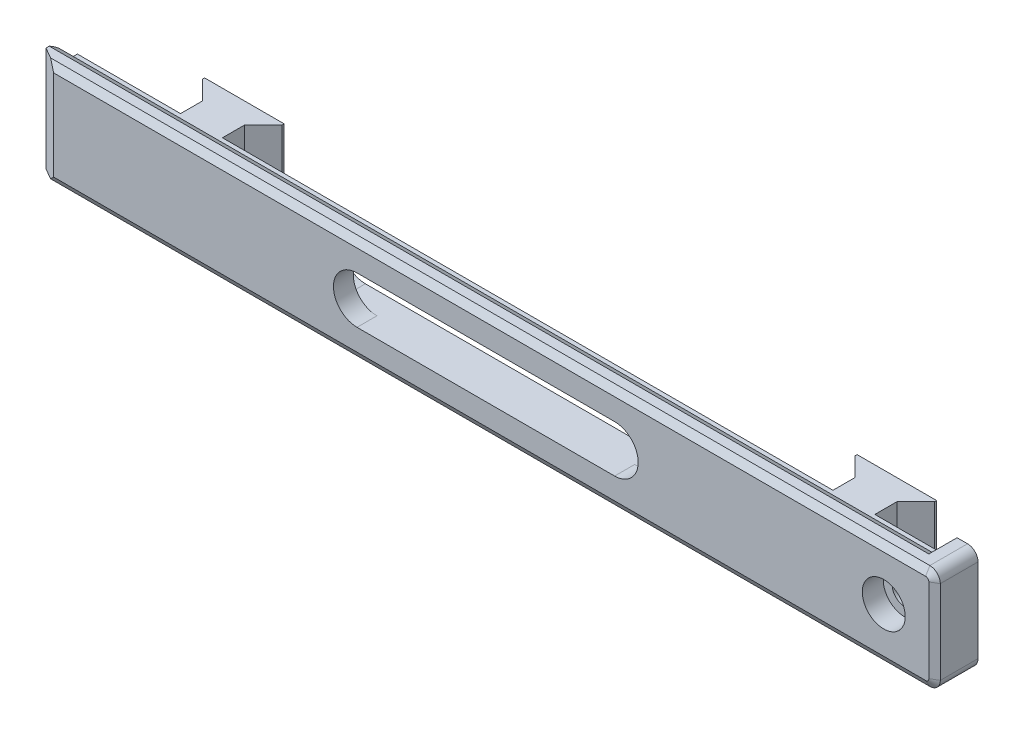
SolidWorks part; units mm, degrees
note: The reader was unsure of these and kept them because the rebuilt part matched: shared geometry of "草图2<3>", "草图5<3>".
ref_plane "前视基准面" through (0, 0, 0) normal (0, 0, 1) x (1, 0, 0)
ref_plane "上视基准面" through (0, 0, 0) normal (0, 1, 0) x (1, 0, 0)
ref_plane "右视基准面" through (0, 0, 0) normal (1, 0, 0) x (0, 0, -1)
sketch "草图1" plane through (0, 0, 0) normal (0, 1, 0) x (1, 0, 0)
  line L0 (-46.8887, 0) -> (50.4859, 0) construction
  line L1 (-43, 2) -> (-33.15, 2)
  line L2 (-43, 2) -> (-43, -2)
  line L3 (-43, -2) -> (43, -2)
  line L4 (43, 2) -> (43, -2)
  line L5 (-43, 2) -> (43, -2) construction
  line L6 (-43, -2) -> (43, 2) construction
  line L7 (-31.15, 5.5725) -> (-31.15, -8.0763) construction
  line L8 (0, -7.558) -> (0, 8.5096) construction
  line L9 (31.15, 4.9966) -> (31.15, -6.291) construction
  line L10 (-33.15, 4.1) -> (-33.15, 2)
  line L14 (-29.15, 4.1) -> (-29.15, 2)
  line L15 (-29.15, 4.1) -> (-27.35, 5.9)
  line L17 (-34.95, 6.1) -> (-27.35, 6.1)
  line L18 (-34.95, 6.1) -> (-34.95, 5.9)
  line L20 (-27.35, 6.1) -> (-27.35, 5.9)
  line L21 (29.15, 4.1) -> (29.15, 2)
  line L22 (33.15, 4.1) -> (33.15, 2)
  line L23 (-29.15, 2) -> (29.15, 2)
  line L24 (-33.15, 4.1) -> (-34.95, 5.9)
  line L25 (33.15, 4.1) -> (34.95, 5.9)
  line L26 (27.35, 6.1) -> (34.95, 6.1)
  line L27 (27.35, 6.1) -> (27.35, 5.9)
  line L28 (34.95, 6.1) -> (34.95, 5.9)
  line L29 (29.15, 4.1) -> (27.35, 5.9)
  line L30 (33.15, 2) -> (43, 2)
  point P0 (0, 0)
  dimension "D1" = 86
  dimension "D2" = 4
  dimension "D3" = 62.3
  dimension "D4" = 31.15
  dimension "D5" = 4
  dimension "D6" = 7.6
  dimension "D7" = 135
  dimension "D8" = 2
  dimension "D9" = 135
  dimension "D10" = 2.1
  dimension "D11" = 4
  dimension "D12" = 135
  dimension "D13" = 135
  dimension "D14" = 2.1
  dimension "D15" = 2
  dimension "D16" = 7.6
extrude "凸台-拉伸1" add sketch "草图1" along normal blind 6
sketch "草图2" plane through (0, 0, -2) normal (0, 0, -1) x (-1, 0, 0)
  line L0 (-12.3, 3) -> (12.3, 3) construction
  line L1 (-12.3, 5.25) -> (12.3, 5.25)
  line L2 (-12.3, 0.75) -> (12.3, 0.75)
  line L3 (-29.15, 6) -> (29.15, 6) construction
  line L4 (-29.15, 0) -> (29.15, 0) construction
  line L5 (0, 0) -> (0, 5.646) construction
  line L6 (-15.5, 3) -> (15.5, 3) construction
  line L7 (-15.5, 5.25) -> (15.5, 5.25)
  line L8 (-15.5, 0.75) -> (15.5, 0.75)
  arc A0 (-12.3, 5.25) -> (-12.3, 0.75) centre (-12.3, 3) ccw
  arc A1 (12.3, 0.75) -> (12.3, 5.25) centre (12.3, 3) ccw
  arc A2 (-15.5, 5.25) -> (-15.5, 0.75) centre (-15.5, 3) ccw
  arc A3 (15.5, 0.75) -> (15.5, 5.25) centre (15.5, 3) ccw
  point P2 (0, 3)
  point P15 (0, 3)
  dimension "D1" = 24.6
  dimension "D2" = 4.5
  dimension "D3" = 31
extrude "切除-拉伸1" cut sketch "草图2" against normal blind 2.1 contours A2 L8 A3 L7
extrude "切除-拉伸2" cut sketch "草图2<3>" against normal blind 4 contours A0 L2 A1 L1
sketch "草图2<3>" plane through (0, 0, -2) normal (0, 0, -1) x (-1, 0, 0) same geometry as "草图2"
sketch "草图3" plane through (0, 0, 2) normal (0, 0, 1) x (1, 0, 0)
  line L0 (43, 6) -> (43, 0) construction
  line L1 (-43, 8) -> (43, 8)
  line L2 (-43, 8) -> (-43, 6)
  line L3 (-43, -2) -> (43, -2)
  line L4 (43, 8) -> (43, 6)
  line L5 (-43, 6) -> (-43, 0) construction
  line L6 (-43, 6) -> (43, 6) construction
  line L7 (-43, 0) -> (43, 0) construction
  line L10 (-43, 0) -> (43, 0)
  line L11 (-43, 6) -> (43, 6)
  line L12 (-43, 0) -> (-43, -2)
  line L13 (43, 0) -> (43, -2)
  dimension "D2" = 2
  dimension "D3" = 2
extrude "凸台-拉伸2" add sketch "草图3" against normal blind 2
sketch "草图4" plane through (0, 0, 2) normal (0, 0, 1) x (1, 0, 0)
  line L0 (43, 8) -> (-43, 8) construction
  line L1 (43, -2) -> (41, -2)
  line L2 (43, -2) -> (43, 8)
  line L3 (43, 8) -> (41, 8)
  line L4 (41, -2) -> (41, 8)
  dimension "D1" = 2
extrude "凸台-拉伸3" add sketch "草图4" against normal blind 4
fillet "圆角1" radius 1 2 edges at (43, -2, 0) (43, 8, 0)
chamfer "倒角1" distance 1 angle 60 1 edges at (-43, 3, 2)
chamfer "倒角2" distance 0.4 angle 60 7 edges at (-1, 8, 0) (-1, -2, 0) (0.366, -2, 2) (42.7071, -1.7071, 2) (43, 3, 2) (42.7071, 7.7071, 2) (0.366, 8, 2)
sketch "草图5" plane through (0, 0, 2) normal (0, 0, 1) x (1, 0, 0)
  line L0 (-41.9608, 8) -> (42, 8) construction
  line L1 (43, 7) -> (43, -1) construction
  circle A0 centre (38, 3) radius 2.05
  circle A1 centre (38, 3) radius 1.2
  dimension "D1" = 5
  dimension "D2" = 4.1
  dimension "D3" = 2.4
  dimension "D4" = 5
extrude "切除-拉伸3" cut sketch "草图5" against normal through all contours A1
extrude "切除-拉伸4" cut sketch "草图5<3>" against normal blind 2 contours A0
sketch "草图5<3>" plane through (0, 0, 2) normal (0, 0, 1) x (1, 0, 0) same geometry as "草图5"
chamfer "倒角3" distance 0.2 angle 60 2 edges at (-43, -0.8, 0) (-43, 6.8, 0)
